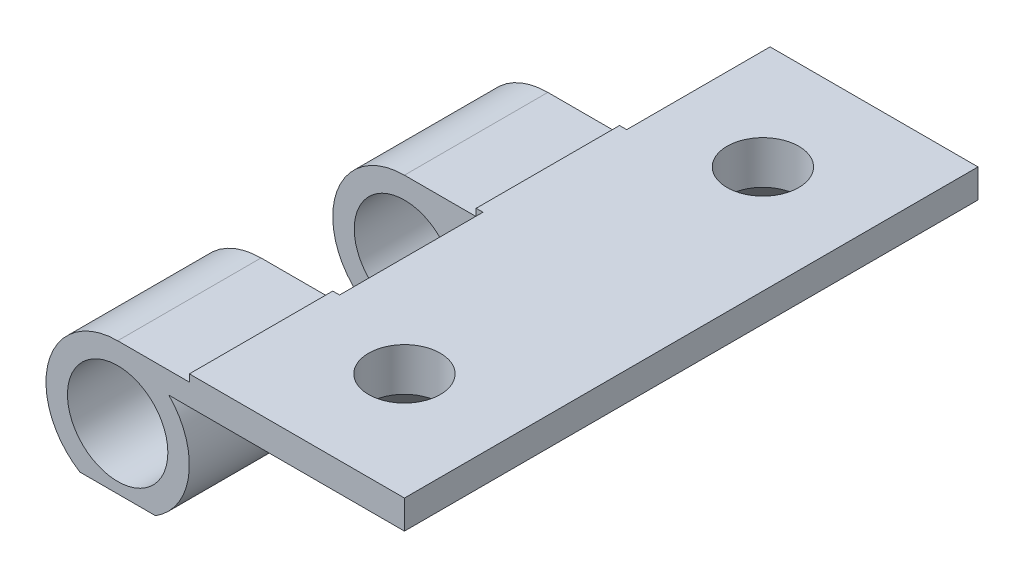
SolidWorks part; units mm, degrees
ref_plane "Ön Düzlem" through (0, 0, 0) normal (0, 0, 1) x (1, 0, 0)
ref_plane "Üst Düzlem" through (0, 0, 0) normal (0, 1, 0) x (1, 0, 0)
ref_plane "Sağ Düzlem" through (0, 0, 0) normal (1, 0, 0) x (0, 0, -1)
sketch "Çizim1" plane through (0, 0, 0) normal (0, 0, 1) x (1, 0, 0)
  line L0 (0, 5) -> (5, 5)
  line L1 (20, 5) -> (20, 0.5)
  line L2 (20, 0.5) -> (4.9749, 0.5)
  line L3 (20, 5) -> (20, 5.5)
  line L4 (20, 5.5) -> (5, 5.5)
  line L5 (5, 5.5) -> (5, 5)
  arc A0 (0, 5) -> (4.9749, 0.5) centre (0, 0) ccw
  circle A1 centre (0, 0) radius 3.5
  dimension "D1" = 10
  dimension "D7" = 7
  dimension "D2" = 20
  dimension "D3" = 4.5
  dimension "D4" = 0.5
  dimension "D5" = 15
  dimension "D6" = 5.5
extrude "Yükseklik-Ekstrüzyon1" add sketch "Çizim1" along normal blind 40
sketch "Çizim2" plane through (0, 0, 40) normal (0, 0, 1) x (1, 0, 0)
  line L0 (-6.3368, -4.25) -> (12.4224, -4.25)
  circle A1 centre (0, 0) radius 3.5 construction
  dimension "D1" = 4.25
extrude "Kes-Ekstrüzyon1" cut sketch "Çizim2" against normal through all and the other way through all flip side to cut
sketch "Çizim3" plane through (0, -4.25, 0) normal (0, -1, 0) x (1, 0, 0)
  line L1 (-5, 30) -> (5, 30)
  line L2 (-5, 30) -> (-5, 20)
  line L3 (-5, 20) -> (5, 20)
  line L4 (5, 30) -> (5, 20)
  line L6 (2.6339, 40) -> (-2.6339, 40) construction
  line L7 (5, 0) -> (-5, 0)
  line L8 (5, 0) -> (5, 10)
  line L9 (5, 10) -> (-5, 10)
  line L10 (-5, 0) -> (-5, 10)
  line L11 (20, 40) -> (20, 0) construction
  dimension "D1" = 10
  dimension "D2" = 10
  dimension "D3" = 10
  dimension "D4" = 10
  dimension "D5" = 10
  dimension "D6" = 15
  dimension "D7" = 15
  dimension "D8" = 10
extrude "Kes-Ekstrüzyon2" cut sketch "Çizim3" against normal through all
sketch "Çizim4" plane through (0, 0.5, 0) normal (0, -1, 0) x (1, 0, 0)
  line L1 (5, 0) -> (20, 0) construction
  line L2 (4.9749, 30) -> (5.4749, 30)
  line L3 (4.9749, 30) -> (4.9749, 20)
  line L4 (4.9749, 20) -> (5.4749, 20)
  line L5 (5.4749, 30) -> (5.4749, 20)
  line L6 (5, 10) -> (5.5, 10)
  line L7 (5, 10) -> (5, 0)
  line L8 (5, 0) -> (5.5, 0)
  line L11 (5.5, 10) -> (5.5, 0)
  dimension "D1" = 0.5
  dimension "D2" = 10
  dimension "D3" = 0.5
sketch "Çizim5" plane through (0, 0.5, 0) normal (0, -1, 0) x (1, 0, 0)
  line L2 (20, 20) -> (42.6437, 20) construction
  line L3 (5, 0) -> (20, 0) construction
  line L4 (20, 40) -> (20, 0) construction
  circle A0 centre (12.5, 7.5) radius 2.5
  circle A1 centre (12.5, 32.5) radius 2.5
  dimension "D1" = 7.5
  dimension "D2" = 7.5
  dimension "D3" = 5
extrude "Kes-Ekstrüzyon4" cut sketch "Çizim5" against normal through all
chamfer "Pah1" distance 3 angle 45 3 edges at (12.5, 0.5, 0) (20, 0.5, 20) (12.4875, 0.5, 40)
extrude "Kes-Ekstrüzyon5" cut sketch "Çizim4" against normal through all
chamfer "Pah2" distance 2 angle 45 2 edges at (12.5, 0.5, 5) (12.5, 0.5, 35)
